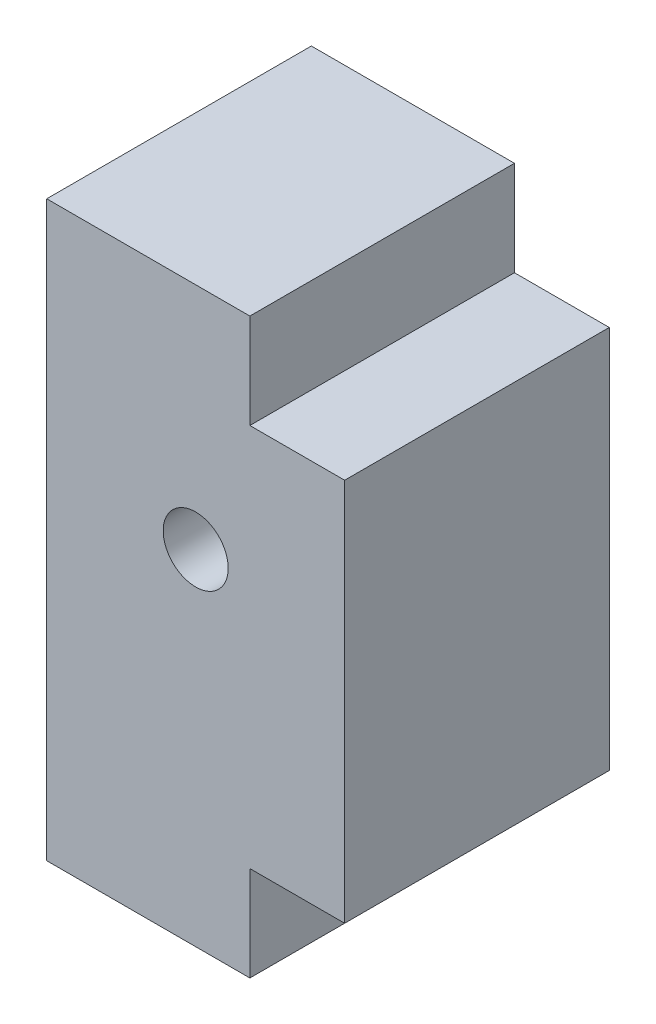
SolidWorks part; units mm, degrees
ref_plane "Front Plane" through (0, 0, 0) normal (0, 0, 1) x (1, 0, 0)
ref_plane "Top Plane" through (0, 0, 0) normal (0, 1, 0) x (1, 0, 0)
ref_plane "Right Plane" through (0, 0, 0) normal (1, 0, 0) x (0, 0, -1)
sketch "Sketch2" plane through (0, 0, 0) normal (0, 0, 1) x (1, 0, 0)
  line L0 (8.25, -152.4) -> (8.25, 152.4) construction
  line L1 (8.25, -39.1052) -> (-8.25, -39.1052)
  line L2 (8.25, -39.1052) -> (8.25, -7.3552)
  line L3 (8.25, -7.3552) -> (-8.25, -7.3552)
  line L4 (-8.25, -39.1052) -> (-8.25, -7.3552)
  line L5 (-8.25, -152.4) -> (-8.25, 152.4) construction
extrude "Boss-Extrude1" add sketch "Sketch2" along normal up to surface (14.655 mm away)
sketch "Sketch3" plane through (0, 0, 14.655) normal (0, 0, 1) x (1, 0, 0)
  line L0 (3.6, -20.0517) -> (3.6, -4.0517) construction
  line L1 (3.6, -23.6517) -> (-3.6, -23.6517)
  line L2 (3.6, -23.6517) -> (3.6, -0.4517)
  line L3 (3.6, -0.4517) -> (-3.6, -0.4517)
  line L4 (-3.6, -23.6517) -> (-3.6, -0.4517)
  line L5 (-4.4, -23.6517) -> (0, -23.6517) construction
  line L6 (0, -0.4517) -> (-4.4, -0.4517) construction
  circle A0 centre (0, -20.0517) radius 2.4 construction
  dimension "D1" = 3.6
extrude "Boss-Extrude2" [suppressed] add sketch "Sketch3" along normal up to surface (6 mm away)
sketch "Sketch4" [suppressed] plane through (0, 0, 11.81) normal (0, 0, 1) x (1, 0, 0)
  circle A4 centre (0, -31.2302) radius 2.8
  circle A5 centre (0, -15.2302) radius 2.8
extrude "Cut-Extrude1" [suppressed] cut sketch "Sketch4" against normal through all
sketch "Sketch5" plane through (0, 0, 14.655) normal (0, 0, 1) x (1, 0, 0)
  line L0 (3, -152.4) -> (3, 152.4) construction
  line L1 (8.25, -39.1052) -> (3, -39.1052)
  line L2 (8.25, -39.1052) -> (8.25, -33.8552)
  line L3 (8.25, -33.8552) -> (3, -33.8552)
  line L4 (3, -39.1052) -> (3, -33.8552)
  line L5 (8.25, -7.3552) -> (3, -7.3552)
  line L6 (8.25, -7.3552) -> (8.25, -12.6052)
  line L7 (8.25, -12.6052) -> (3, -12.6052)
  line L8 (3, -7.3552) -> (3, -12.6052)
extrude "Cut-Extrude2" cut sketch "Sketch5" against normal through all
sketch "Sketch6" plane through (0, 0, 14.655) normal (0, 0, 1) x (1, 0, 0)
  circle A0 centre (0, -4.0517) radius 2.4 construction
  circle A1 centre (0, -20.0517) radius 2.4 construction
  circle A2 centre (0, -4.0517) radius 2.4 construction
  circle A3 centre (0, -20.0517) radius 2.4 construction
  circle A4 centre (0, -20.0517) radius 1.8
  circle A5 centre (0, -4.0517) radius 1.8
  dimension "D1" = 0.6
extrude "Cut-Extrude3" cut sketch "Sketch6" against normal through all
